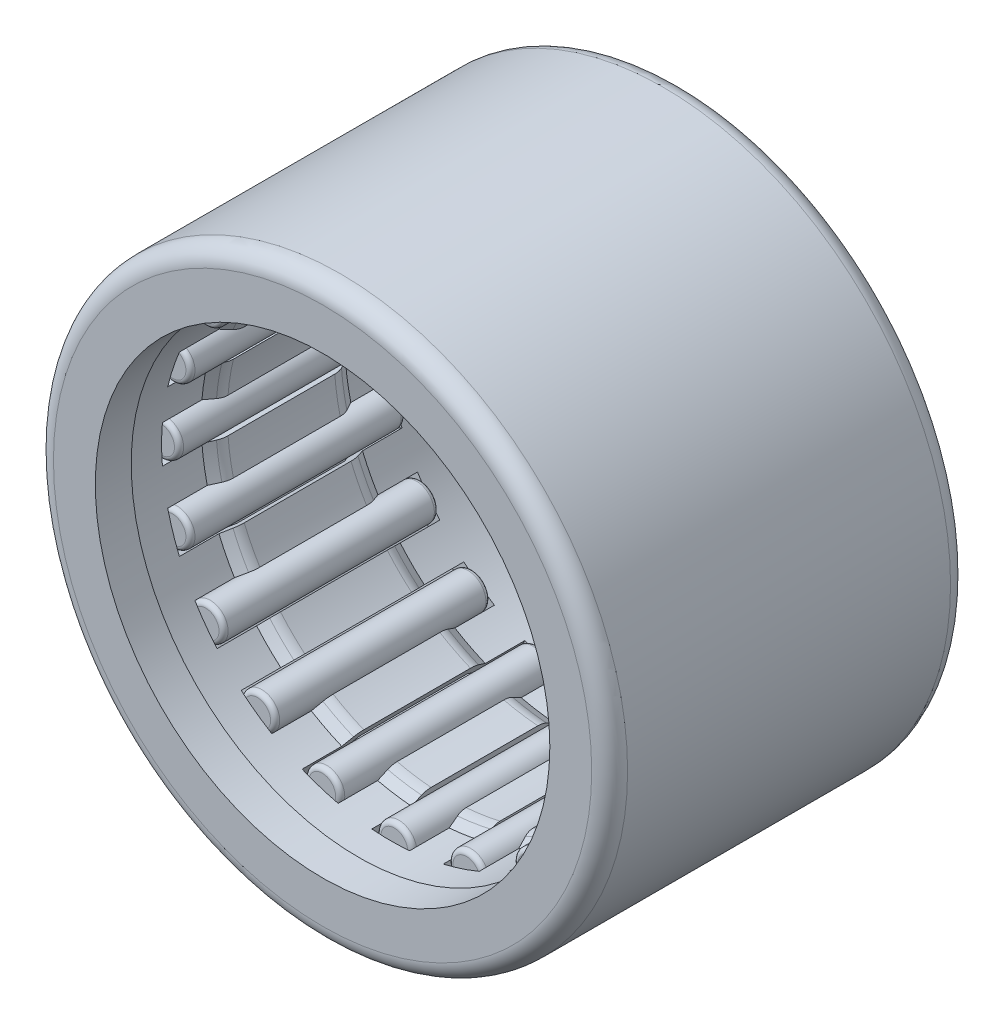
SolidWorks part; units mm, degrees
material "Plain Carbon Steel"
ref_plane "Front Plane" through (0, 0, 0) normal (0, 0, 1) x (1, 0, 0)
ref_plane "Top Plane" through (0, 0, 0) normal (0, 1, 0) x (1, 0, 0)
ref_plane "Right Plane" through (0, 0, 0) normal (1, 0, 0) x (0, 0, -1)
sketch "Sketch1" plane through (0, 0, 0) normal (0, 0, 1) x (1, 0, 0)
  circle A0 centre (0, 0) radius 6
  circle A1 centre (0, 0) radius 8
  dimension "OD" = 16
  dimension "ID" = 12
sketch "Sketch2" plane through (0, 0, 0) normal (1, 0, 0) x (0, 0, -1)
  line L0 (-5, 0) -> (5, 0) construction
  line L2 (-5, -6) -> (-5, 6) construction
  line L3 (5, 8) -> (-5, 8) construction
  line L11 (0, 0) -> (0, 8) construction
  line L16 (5, -8) -> (5, 8) construction
  line L17 (-5, 6) -> (5, 6) construction
  line L18 (-5, -6) -> (5, -6) construction
  point P4 (0, 0)
  point P8 (0, 8)
  point P10 (-5, 0)
  dimension "For Shaft Diameter" = 12
  dimension "Width" = 10
  dimension "For Housing ID" = 16
sketch "Sketch3" plane through (0, 0, 0) normal (1, 0, 0) x (0, 0, -1)
  line L0 (-5, -6) -> (-5, 6) construction
  line L2 (0, 8) -> (0, 7.3333) construction
  line L3 (0, 7.3333) -> (0, 6.6667) construction
  line L4 (0, 6.6667) -> (0, 6) construction
  line L16 (4, 7.3333) -> (4, 6.3333)
  line L17 (4, 6.3333) -> (5, 6.3333)
  line L18 (5, 6.3333) -> (5, 8)
  line L19 (5, 8) -> (-5, 8)
  line L20 (-5, 8) -> (-5, 6.3333)
  line L21 (-5, 6.3333) -> (-4, 6.3333)
  line L22 (-4, 6.3333) -> (-4, 7.3333)
  line L23 (-4, 7.3333) -> (4, 7.3333)
  point P17 (0, 6.3333)
  dimension "D1" = 8
revolve "Revolve1" add sketch "Sketch3" angle 360 about L0
fillet "Fillet1" radius 0.5 2 edges at (8, 0, -5) (8, 0, 5)
sketch "Sketch4" plane through (0, 0, 0) normal (1, 0, 0) x (0, 0, -1)
  line L0 (0, 7) -> (0, 6.5) construction
  line L2 (-5, 6.3333) -> (-4, 6.3333) construction
  line L3 (-3, 6) -> (3, 6)
  line L4 (-3, 6) -> (-3, 6.5)
  line L5 (-3, 6.5) -> (3, 6.5)
  line L6 (3, 6) -> (3, 6.5)
  line L7 (0, 7.3333) -> (0, 6.6667) construction
  line L8 (-3, 6.25) -> (3, 6.25) construction
  line L9 (-4, 6.3333) -> (-3, 6.3333) construction
  point P15 (3.1016, 6.3333)
  point P16 (-3.1016, 6.3333)
  dimension "D1" = 0.1016
revolve "Revolve2" add sketch "Sketch4" angle 360 about L5
fillet "Fillet2" radius 0.127 2 edges at (0.5, 6.5, 3) (0.5, 6.5, -3)
sketch "Sketch5" plane through (0, 0, 0) normal (0, 0, 1) x (1, 0, 0)
  line L0 (0, 0) -> (0.5, 6.5) construction
  line L1 (0, -6) -> (0, 6) construction
  line L2 (0.5, 6.5) -> (-0.5, 6.5) construction
  line L3 (-0.5, 6.5) -> (0, 0) construction
  circle A0 centre (0, 6.5) radius 0.5
  circle A1 centre (0, 6.5) radius 0.5
  dimension "D1" = 8.797
pattern_circular "CirPattern1" count 20 over 360 about axis through (0, 0, 5) along (0, 0, -1) of bodies 105
sketch "Sketch6" plane through (0, 0, 0) normal (1, 0, 0) x (0, 0, -1)
  line L0 (0, 6.3333) -> (0, 6.6667) construction
  line L1 (-4, 6.3841) -> (4, 6.3841) construction
  line L2 (-4, 6.3841) -> (-4, 6.8333)
  line L3 (-4, 6.8333) -> (-2.2758, 6.8333) construction
  line L5 (-4, 6.3841) -> (-2, 6.3841)
  line L6 (-2, 6.3841) -> (-1.6233, 6.1667)
  line L7 (-1.6233, 6.1667) -> (1.6233, 6.1667)
  line L8 (4, 7.3333) -> (4, 6.3333) construction
  line L9 (-4, 6.3333) -> (-4, 7.3333) construction
  line L10 (-5, 6.3333) -> (-4, 6.3333) construction
  line L13 (0, 6) -> (0, 6.3333) construction
  line L14 (0, 6.6667) -> (0, 6) construction
  line L15 (2, 6.3841) -> (1.6233, 6.1667)
  line L16 (-4, 6.8333) -> (-2.2758, 6.8333)
  line L17 (-2.2758, 6.8333) -> (-1.4978, 6.3841)
  line L18 (-1.4978, 6.3841) -> (1.4978, 6.3841)
  line L21 (-1.6233, 6.1667) -> (-1.4978, 6.3841) construction
  line L22 (4, 6.3841) -> (2, 6.3841)
  line L23 (4, 6.3841) -> (4, 6.8333)
  line L24 (4, 6.8333) -> (2.2758, 6.8333)
  line L25 (2.2758, 6.8333) -> (1.4978, 6.3841)
  line L26 (0, 6) -> (-1, 6) construction
  line L29 (-3, 6) -> (3, 6) construction
  line L30 (-1, 6) -> (-2, 6) construction
  line L31 (-2, 6) -> (-3, 6) construction
  point P10 (0, 6.1667)
  point P18 (0, 6.3333)
  point P24 (0, 6.1667)
  point P28 (0, 6.3841)
  dimension "D1" = 0.0508
  dimension "D2" = 30
revolve "Revolve3" add sketch "Sketch6" angle 360 about L0
fillet "Fillet3" radius 0.508 2 edges at (6.1667, 0, 1.6233) (6.1667, 0, -1.6233)
sketch "Sketch7" plane through (0, 0, 0) normal (0, 0, 1) x (1, 0, 0)
  line L0 (0, 6) -> (0, 6.5) construction
  line L1 (0, 6) -> (0, 6.5) construction
  line L3 (-0.4537, 5.9492) -> (0.4537, 5.9492)
  line L4 (-0.4537, 5.9492) -> (-0.6479, 7.0508)
  line L5 (-0.6479, 7.0508) -> (0.6479, 7.0508)
  line L6 (0.4537, 5.9492) -> (0.6479, 7.0508)
  line L7 (0, 7.0508) -> (0, 5.9492) construction
  line L8 (-0.5508, 6.5) -> (0.5508, 6.5) construction
  circle A0 centre (0, 6.5) radius 0.5 construction
  circle A1 centre (0, 6.5) radius 0.5508 construction
  dimension "D2" = 20
  dimension "D1" = 0.0508
extrude "Cut-Extrude1" cut sketch "Sketch7" along normal up to vertex (3.1016 mm away) and the other way up to vertex (3.1016 mm away) up to point (0, 6.3333, 3.1016) other way up to point (0, 6.3333, -3.1016)
pattern_circular "CirPattern2" count 20 over 360 about axis through (0, 0, 5) along (0, 0, -1) of "Cut-Extrude1"
equation "\"D1@Fillet1\" =  ( \"OD@Sketch1\" - \"For Shaft Diameter@Sketch2\" )  * .125"
equation "\"D1@CirPattern1\" = 360 / \"D1@Sketch5\" / 2"
equation "\"D2\"= \"D1\""
equation "\"D1@CirPattern2\" = \"D1@CirPattern1\""
equation "\"D1@Sketch3\" = \"Width@Sketch2\" * .8"
